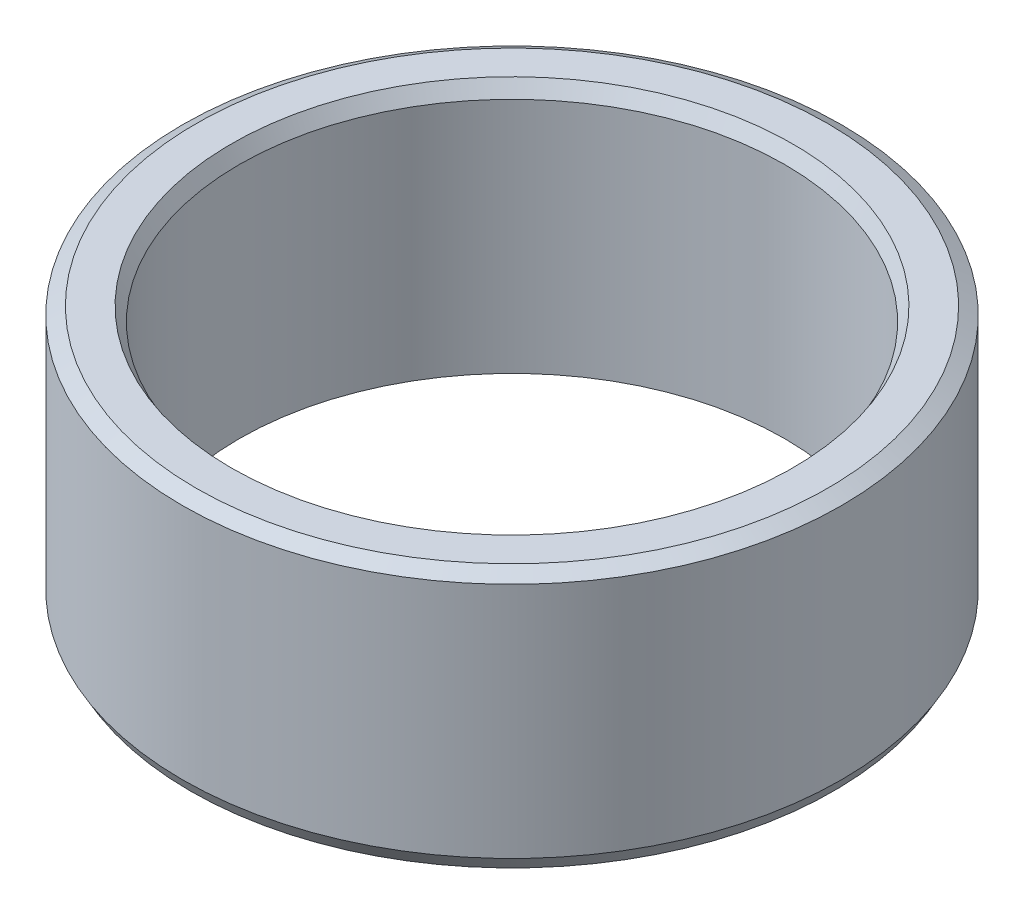
SolidWorks part; units mm, degrees
ref_plane "Front Plane" through (0, 0, 0) normal (0, 0, 1) x (1, 0, 0)
ref_plane "Top Plane" through (0, 0, 0) normal (0, 1, 0) x (1, 0, 0)
ref_plane "Right Plane" through (0, 0, 0) normal (1, 0, 0) x (0, 0, -1)
sketch "Sketch1" plane through (0, 0, 0) normal (0, 1, 0) x (1, 0, 0)
  circle A0 centre (0, 0) radius 52.5
  dimension "SLEEVE_OD" = 105
extrude "Boss-Extrude1" add sketch "Sketch1" along normal blind 41.2904
sketch "Sketch2" plane through (0, 0, 0) normal (0, 1, 0) x (1, 0, 0)
  circle A0 centre (0, 0) radius 43.4219
  dimension "BORE_D" = 86.8439
extrude "Cut-Extrude1" cut sketch "Sketch2" along normal through all
chamfer "Chamfer1" distance 1.2751 angle 60 4 edges at (0, 41.2904, 43.4219) (0, 0, 43.4219) (0, 0, 52.5) (0, 41.2904, 52.5) first distance on face at (0, 41.2904, 43.4219) first distance on face at (0, 0, 43.4219) first distance on face at (0, 41.2904, 52.5)
